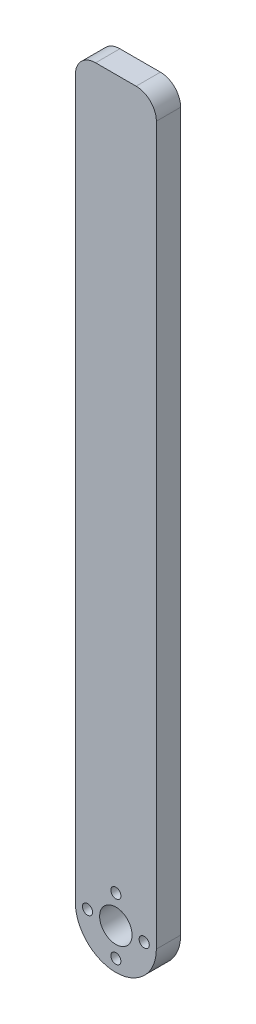
SolidWorks part; units mm, degrees
ref_plane "Front" through (0, 0, 0) normal (0, 0, 1) x (1, 0, 0)
ref_plane "Top" through (0, 0, 0) normal (0, 1, 0) x (1, 0, 0)
ref_plane "Right" through (0, 0, 0) normal (1, 0, 0) x (0, 0, -1)
sketch "Esquisse1" plane through (0, 0, 0) normal (0, 0, 1) x (1, 0, 0)
  line L1 (0, 0) -> (20, 0)
  line L2 (0, 0) -> (0, 192)
  line L3 (0, 192) -> (20, 192)
  line L4 (20, 0) -> (20, 192)
  dimension "D1" = 20
  dimension "D2" = 192
extrude "Boss.-Extru.1" add sketch "Esquisse1" along normal blind 6
sketch "Esquisse2" plane through (0, 0, 6) normal (0, 0, 1) x (1, 0, 0)
  line L0 (10, 0) -> (10, 10) construction
  line L1 (0, 0) -> (20, 0) construction
  line L2 (10, 10) -> (0, 10) construction
  line L3 (0, 192) -> (0, 0) construction
  circle A0 centre (10, 10) radius 4
  dimension "D2" = 8
  dimension "D1" = 10
extrude "Enlèv. mat.-Extru.1" cut sketch "Esquisse2" against normal through all both and the other way through all
fillet "Congé1" radius 10 2 edges at (20, 0, 3) (0, 0, 3)
fillet "Congé2" radius 5 2 edges at (20, 192, 3) (0, 192, 3)
sketch "Esquisse3" plane through (0, 0, 6) normal (0, 0, 1) x (1, 0, 0)
  line L0 (10, 17) -> (10, 10) construction
  circle A0 centre (10, 17) radius 1.25
  circle A1 centre (17, 10) radius 1.25
  circle A2 centre (10, 3) radius 1.25
  circle A3 centre (3, 10) radius 1.25
  point P12 (10, 10)
  dimension "D2" = 2.5
  dimension "D1" = 7
  dimension "D3" = 4
extrude "Enlèv. mat.-Extru.2" cut sketch "Esquisse3" against normal through all both and the other way through all
